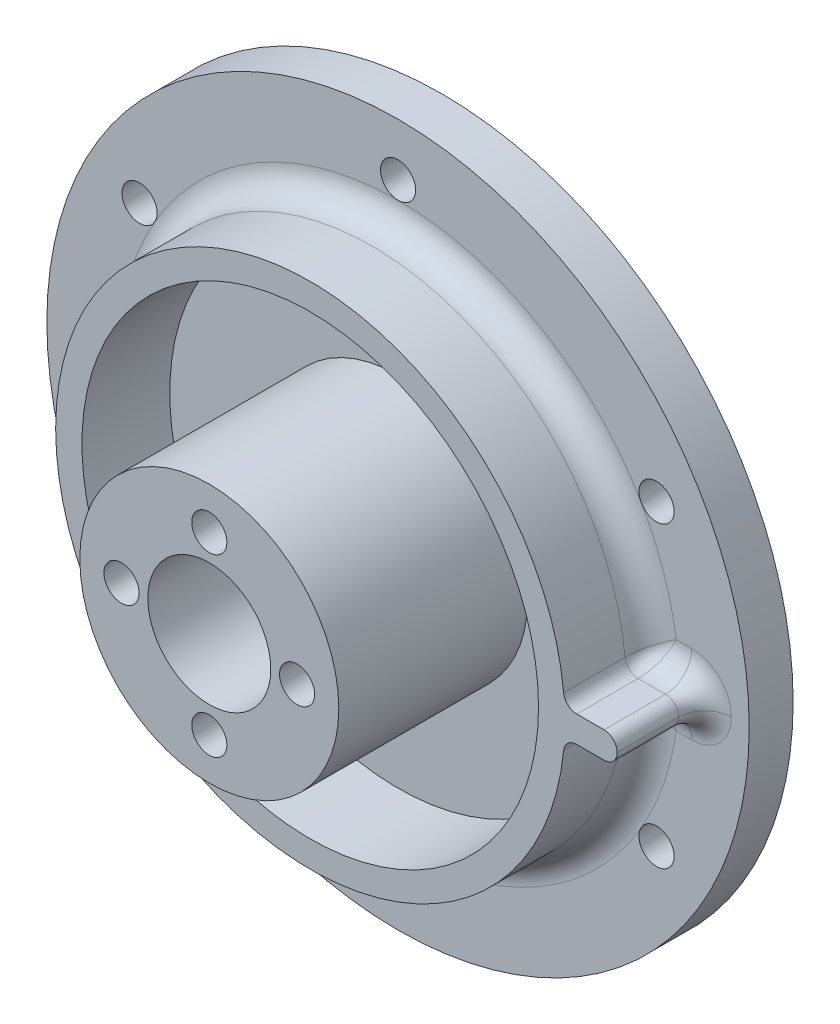
SolidWorks part; units mm, degrees
ref_plane "Plano frontal" through (0, 0, 0) normal (0, 0, 1) x (1, 0, 0)
ref_plane "Plano superior" through (0, 0, 0) normal (0, 1, 0) x (1, 0, 0)
ref_plane "Plano direito" through (0, 0, 0) normal (1, 0, 0) x (0, 0, -1)
sketch "Esboço1" plane through (0, 0, 0) normal (0, 0, 1) x (1, 0, 0)
  circle A0 centre (0, 0) radius 40
  circle A1 centre (0, 34) radius 2
  circle A2 centre (29.4449, 17) radius 2
  circle A3 centre (29.4449, -17) radius 2
  circle A4 centre (0, -34) radius 2
  circle A5 centre (-29.4449, -17) radius 2
  circle A6 centre (-29.4449, 17) radius 2
  point P18 (0, 0)
  dimension "D1" = 80
  dimension "D2" = 4
  dimension "D3" = 34
  dimension "D4" = 6
extrude "Ressalto-extrusão1" add sketch "Esboço1" along normal blind 5
sketch "Esboço2" plane through (0, 0, 5) normal (0, 0, 1) x (1, 0, 0)
  circle A0 centre (0, 0) radius 14.75
  dimension "D1" = 29.5
extrude "Ressalto-extrusão2" add sketch "Esboço2" along normal blind 21.5
sketch "Esboço3" plane through (0, 0, 26.5) normal (0, 0, 1) x (1, 0, 0)
  circle A0 centre (0, 10) radius 2
  circle A1 centre (10, 0) radius 2
  circle A2 centre (0, -10) radius 2
  circle A3 centre (-10, 0) radius 2
  circle A4 centre (0, 0) radius 7
  point P12 (0, 0)
  dimension "D1" = 4
  dimension "D2" = 10
  dimension "D4" = 14
  dimension "D3" = 4
extrude "Corte-extrusão1" cut sketch "Esboço3" against normal up to surface (26.5 mm away) up to face at (40, 0, 0)
sketch "Esboço4" plane through (0, 0, 5) normal (0, 0, 1) x (1, 0, 0)
  line L0 (34.9612, -1.5) -> (28.9612, -1.5)
  line L1 (34.9612, 1.5) -> (34.9612, -1.5)
  line L2 (34.9612, 1.5) -> (28.9612, 1.5)
  circle A0 centre (0, 0) radius 26
  arc A1 (28.9612, 1.5) -> (28.9612, -1.5) centre (0, 0) ccw
  point P9 (34.9612, 0)
  dimension "D1" = 52
  dimension "D2" = 58
  dimension "D3" = 6
  dimension "D4" = 3
extrude "Ressalto-extrusão3" add sketch "Esboço4" along normal blind 10
fillet "Filete1" radius 1.5 4 edges at (28.9612, 1.5, 10) (28.9612, -1.5, 10) (34.9612, 1.5, 10) (34.9612, -1.5, 10)
fillet "Filete2" radius 3 7 edges at (29.345, 1.8884, 5) (31.9066, 1.5, 5) (34.5218, 1.0607, 5) (34.5218, -1.0607, 5) (31.9066, -1.5, 5) (29.345, -1.8884, 5) (-29, 0, 5)
